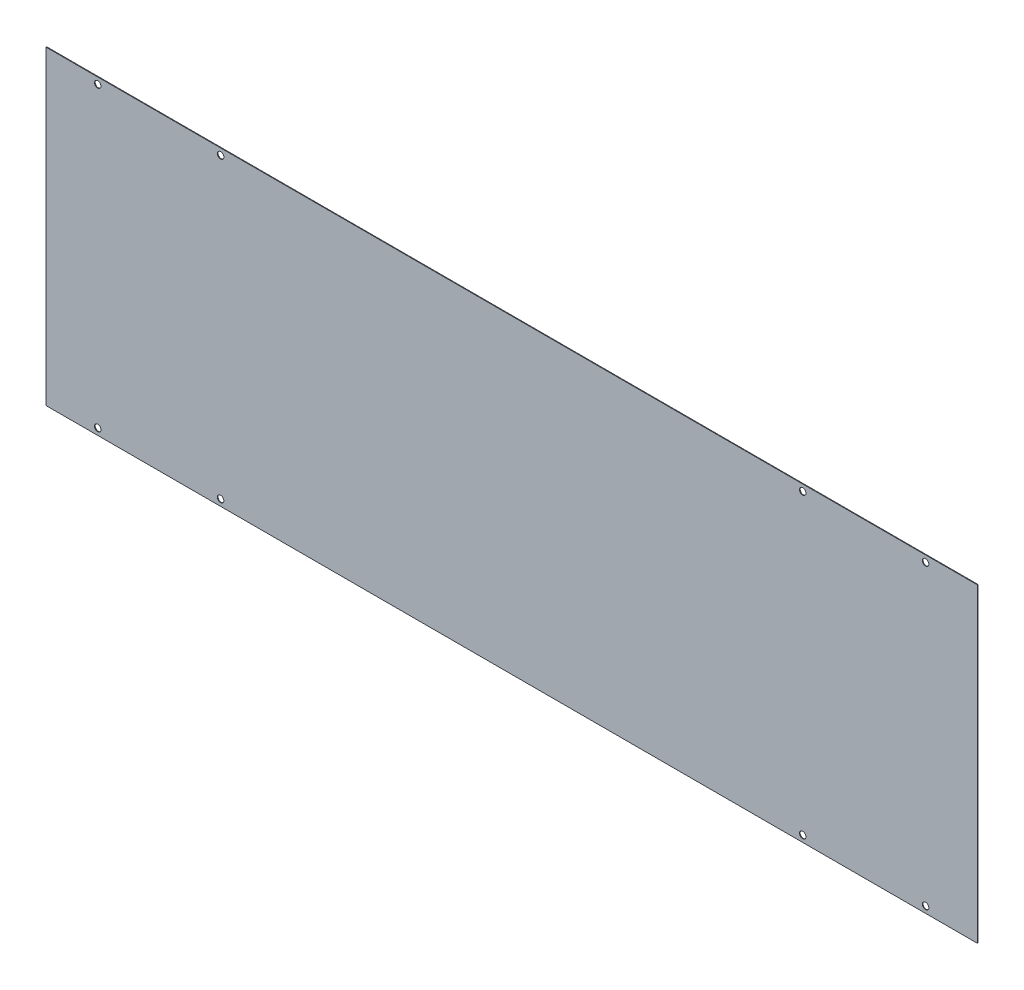
SolidWorks part; units mm, degrees
ref_plane "Front Plane" through (0, 0, 0) normal (0, 0, 1) x (1, 0, 0)
ref_plane "Top Plane" through (0, 0, 0) normal (0, 1, 0) x (1, 0, 0)
ref_plane "Right Plane" through (0, 0, 0) normal (1, 0, 0) x (0, 0, -1)
sketch "Sketch1" plane through (0, 0, 0) normal (0, 0, 1) x (1, 0, 0)
  line L1 (-457.2, -152.4) -> (457.2, -152.4)
  line L2 (-457.2, -152.4) -> (-457.2, 152.4)
  line L3 (-457.2, 152.4) -> (457.2, 152.4)
  line L4 (457.2, -152.4) -> (457.2, 152.4)
  line L5 (-457.2, -152.4) -> (457.2, 152.4) construction
  line L6 (-457.2, 152.4) -> (457.2, -152.4) construction
  point P0 (0, 0)
  dimension "D1" = 914.4
  dimension "D2" = 304.8
extrude "Boss-Extrude1" add sketch "Sketch1" along normal blind 0.635
hole_wizard "1/4 (0.25) Diameter Hole1" positions "Sketch2" profile "Sketch3" hole size "1/4" standard "ANSI Inch" end condition through all
sketch "Sketch2" plane through (0, 0, 0.635) normal (0, 0, 1) x (1, 0, 0)
  line L0 (457.2, 152.4) -> (-457.2, 152.4) construction
  line L1 (-457.2, -152.4) -> (457.2, -152.4) construction
  line L2 (457.2, -152.4) -> (457.2, 152.4) construction
  point P0 (285.75, 146.05)
  point P2 (406.4, 146.05)
  point P4 (406.4, -146.05)
  point P6 (285.75, -146.05)
  dimension "D1" = 6.35
  dimension "D2" = 6.35
  dimension "D3" = 50.8
  dimension "D4" = 171.45
sketch "Sketch3" plane through (285.75, 146.05, 0.635) normal (1, 0, 0) x (0, -1, 0)
  line L0 (0, 0) -> (0, 0.635)
  line L1 (0, 0.635) -> (3.175, 0.635)
  line L2 (3.175, 0.635) -> (3.175, 0)
  line L5 (3.175, 0) -> (0, 0)
  line L11 (0, -6.35) -> (0, 107.95) construction
  dimension "Thru Hole Dia." = 6.35
  dimension "Thru Hole Depth" = 0.635
mirror "Mirror1" about plane through (0, 0, 0) normal (1, 0, 0) of "1/4 (0.25) Diameter Hole1"
